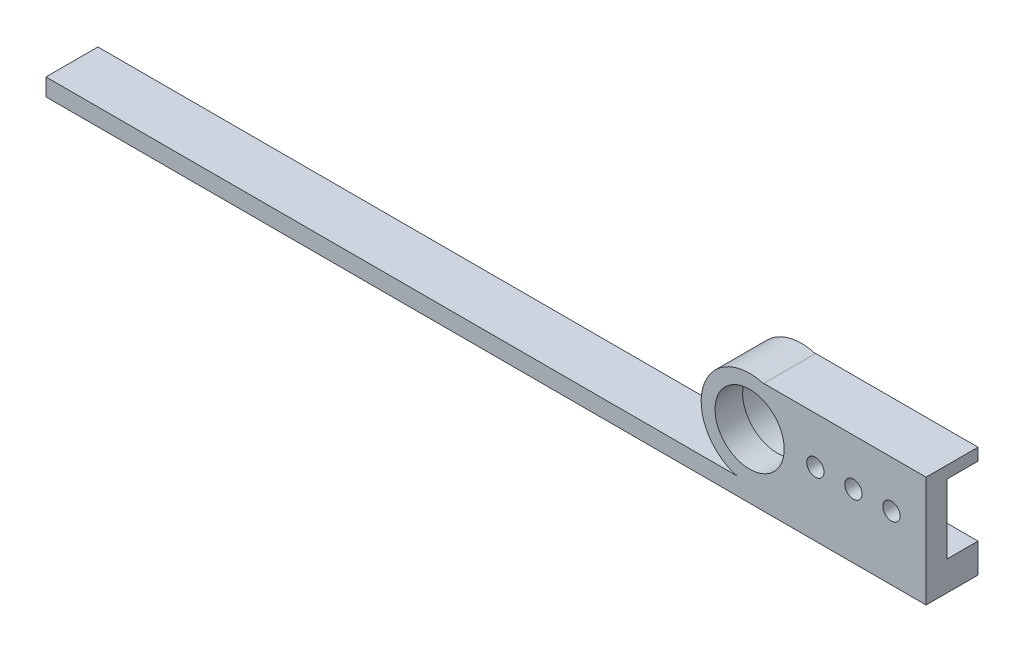
SolidWorks part; units mm, degrees
ref_plane "前视基准面" through (0, 0, 0) normal (0, 0, 1) x (1, 0, 0)
ref_plane "上视基准面" through (0, 0, 0) normal (0, 1, 0) x (1, 0, 0)
ref_plane "右视基准面" through (0, 0, 0) normal (1, 0, 0) x (0, 0, -1)
sketch "草图1" plane through (0, 0, 0) normal (0, 0, 1) x (1, 0, 0)
  line L1 (20, -10) -> (-20, -10)
  line L2 (20, -10) -> (20, 10)
  line L3 (20, 10) -> (-20, 10)
  line L4 (-20, -10) -> (-20, 10)
  line L5 (20, -10) -> (-20, 10) construction
  line L6 (20, 10) -> (-20, -10) construction
  point P0 (0, 0)
  dimension "D1" = 40
  dimension "D2" = 20
extrude "凸台-拉伸1" add sketch "草图1" along normal blind 6
sketch "草图2" plane through (0, 0, 6) normal (0, 0, 1) x (1, 0, 0)
  line L0 (20, -10) -> (20, 10) construction
  circle A0 centre (10, 0) radius 2.5
  circle A1 centre (-1, 0) radius 2.5
  circle A2 centre (-12, 0) radius 2.5
  dimension "D1" = 10
  dimension "D2" = 5
  dimension "D3" = 3
extrude "切除-拉伸1" cut sketch "草图2" against normal through all
sketch "草图3" plane through (0, 0, 6) normal (0, 0, 1) x (1, 0, 0)
  line L0 (20, 13.5) -> (20, 10)
  line L1 (20, -13.5) -> (-26.894, -13.5)
  line L3 (20, 13.5) -> (-26.894, 13.5)
  line L4 (-20, 10) -> (-20, -10)
  line L5 (-20, -10) -> (20, -10)
  line L6 (20, -10) -> (20, 10)
  line L7 (20, 10) -> (-20, 10)
  line L8 (-20, 10) -> (-20, -10)
  line L9 (-20, -10) -> (20, -10)
  line L10 (20, -10) -> (20, 10)
  line L11 (20, 10) -> (-20, 10)
  line L12 (-26.894, -13.5) -> (-26.894, 13.5)
  line L13 (20, -10.0394) -> (-26.894, 13.5) construction
  line L14 (20, 10.0394) -> (-26.894, -13.5) construction
  line L15 (20, -10) -> (20, -13.5)
  circle A0 centre (-31, 0) radius 11
  circle A1 centre (-31, 0) radius 14
  point P2 (0, 0)
  line M10 (-20, 10) -> (-20, -10)
  line M11 (-20, -10) -> (20, -10)
  line M13 (20, 10) -> (-20, 10)
  dimension "D3" = 22
  dimension "D4" = 28
  dimension "D2" = 3.5
  dimension "D1" = 0
extrude "凸台-拉伸2" add sketch "草图3" against normal blind 15 contours L3 A1 L1 L12 A0 | A1 L1 L15 M11 M10 | L1 A1 L8 A0 L12 | L8 A1 L3 L12 A0 | L8 A1 | A1 L0 L3 M10 M13 region at (-1.9449, 11.7771, 6) region at (-1.9449, -11.7771, 6) region at (-23.0173, 9.0328, 6) region at (-27.2274, 11.7946, 6) region at (-18.7882, 0, 6) region at (-23.0173, -9.0328, 6)
sketch "草图5" plane through (0, 0, 6) normal (0, 0, 1) x (1, 0, 0)
  circle A0 centre (-31, 0) radius 10
  circle A1 centre (-31, 0) radius 11 construction
  circle A2 centre (-31, 0) radius 11
  dimension "D1" = 20
extrude "凸台-拉伸3" add sketch "草图5" against normal blind 8
sketch "草图6" plane through (0, 0, 6) normal (0, 0, 1) x (1, 0, 0)
  circle A0 centre (-31, 0) radius 8.5
  circle A1 centre (-31, 0) radius 10 construction
  circle A2 centre (-31, 0) radius 10
  dimension "D1" = 17
sketch "草图8" plane through (0, 0, 6) normal (0, 0, 1) x (1, 0, 0)
  line L0 (20, -13.5) -> (20, 13.5) construction
  line L1 (20, -13.5) -> (-26.894, -13.5) construction
  line L2 (20, 13.5) -> (-26.894, 13.5) construction
  line L3 (20, -13.5) -> (20, 13.5)
  line L4 (20, -13.5) -> (-26.894, -13.5)
  line L5 (20, 13.5) -> (-26.894, 13.5)
  line L6 (-45, -14) -> (-26.894, -13.5)
  line L7 (-45, -14) -> (-239, -14)
  line L8 (-45, -14) -> (-45, 14)
  line L9 (-45, 14) -> (-239, 14)
  line L10 (-239, -14) -> (-239, 14)
  line L11 (-45, -14) -> (-239, 14) construction
  line L12 (-45, 14) -> (-239, -14) construction
  line L13 (-45, 14) -> (-26.894, 13.3843)
  line L14 (-12, 0) -> (-31, 0)
  arc A0 (-26.894, 13.3843) -> (-26.894, -13.3843) centre (-31, 0) ccw construction
  arc A1 (-26.894, 13.3843) -> (-26.894, -13.3843) centre (-31, 0) ccw
  point P6 (-142, 0)
  dimension "D1" = 28
  dimension "D2" = 194
  dimension "D3" = 14
sketch "草图9" plane through (0, -13.5, 0) normal (0, -1, 0) x (1, 0, 0)
  circle A0 centre (10.5344, 0) radius 5.2388
sketch "草图10" plane through (20, 0, 0) normal (1, 0, 0) x (0, 0, -1)
  line L1 (9, -13.5) -> (-6, -13.5)
  line L2 (9, -13.5) -> (9, -18.5)
  line L3 (9, -18.5) -> (-6, -18.5)
  line L4 (-6, -13.5) -> (-6, -18.5)
  dimension "D1" = 5
extrude "凸台-拉伸4" add sketch "草图10" against normal blind 500
sketch "草图11" plane through (0, 0, -9) normal (0, 0, -1) x (-1, 0, 0)
  line L1 (22.0371, -11.3638) -> (33.5283, -11.3638)
  line L2 (22.0371, -11.3638) -> (22.0371, -16.4864)
  line L3 (22.0371, -16.4864) -> (33.5283, -16.4864)
  line L4 (33.5283, -11.3638) -> (33.5283, -16.4864)
extrude "凸台-拉伸5" add sketch "草图11" against normal through all
sketch "草图12" plane through (0, -18.5, 0) normal (0, -1, 0) x (1, 0, 0)
  line L0 (-234.3163, -11.9161) -> (-234.3163, 6)
  line L1 (-234.3163, 118.5858) -> (-234.3163, -251.4142) construction
  line L2 (-234.3163, -11.9161) -> (-95.8824, -11.9161) construction
  line L3 (-480, 6) -> (20, 6) construction
sketch "草图13" plane through (0, -18.5, 0) normal (0, -1, 0) x (1, 0, 0)
  line L1 (-234.3163, -11.9161) -> (-490.0472, -11.9161)
  line L2 (-234.3163, -11.9161) -> (-234.3163, 14.9475)
  line L3 (-234.3163, 14.9475) -> (-490.0472, 14.9475)
  line L4 (-490.0472, -11.9161) -> (-490.0472, 14.9475)
extrude "切除-拉伸2" cut sketch "草图13" against normal through all
